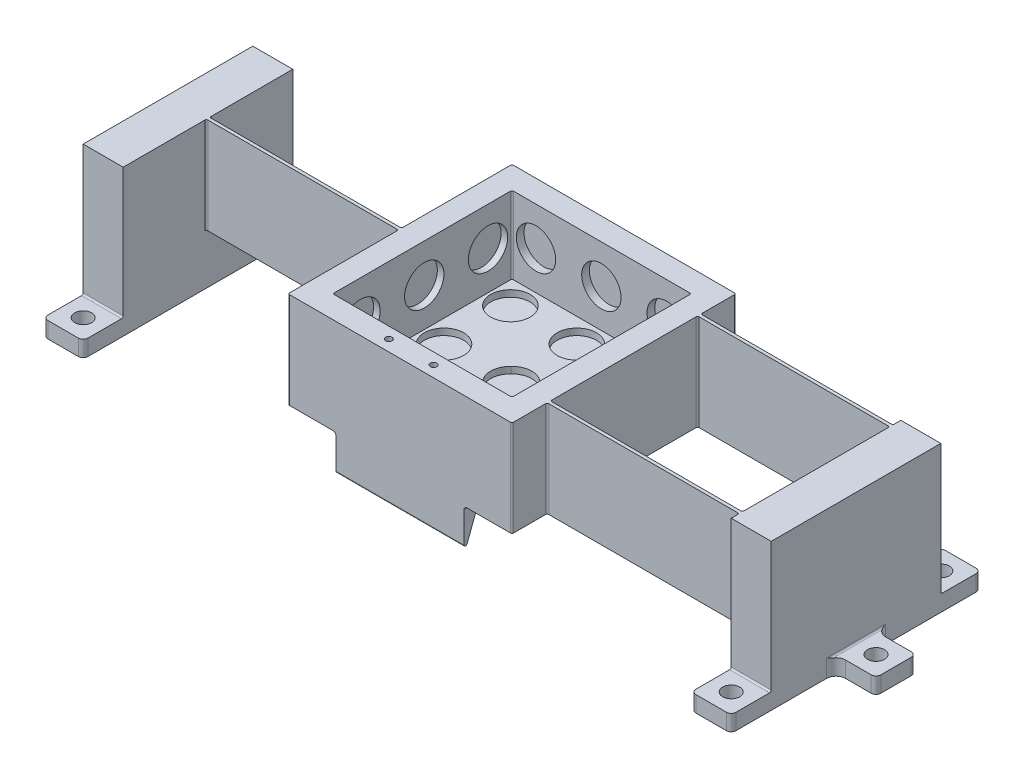
SolidWorks part; units mm, degrees
ref_plane "Front Plane" through (0, 0, 0) normal (0, 0, 1) x (1, 0, 0)
ref_plane "Top Plane" through (0, 0, 0) normal (0, 1, 0) x (1, 0, 0)
ref_plane "Right Plane" through (0, 0, 0) normal (1, 0, 0) x (0, 0, -1)
sketch "Sketch1" plane through (0, 0, 0) normal (0, 1, 0) x (1, 0, 0)
  line L1 (-35, -35) -> (35, -35)
  line L2 (-35, -35) -> (-35, 35)
  line L3 (-35, 35) -> (35, 35)
  line L4 (35, -35) -> (35, 35)
  line L5 (-35, -35) -> (35, 35) construction
  line L6 (-35, 35) -> (35, -35) construction
  point P0 (0, 0)
  dimension "D1" = 70
  dimension "D2" = 70
extrude "Boss-Extrude1" add sketch "Sketch1" along normal blind 30
shell "Shell1" thickness 7 removed face at (0, 30, 0)
sketch "Sketch2" plane through (0, 30, 0) normal (0, 1, 0) x (1, 0, 0)
  line L0 (-35, 35) -> (-35, -35) construction
  line L1 (-28, -28) -> (28, -28) construction
  line L2 (-28, -28) -> (-28, 28) construction
  line L3 (-28, 28) -> (28, 28) construction
  line L4 (28, -28) -> (28, 28) construction
  line L5 (-28, -28) -> (28, 28) construction
  line L6 (-28, 28) -> (28, -28) construction
  line L7 (35, 35) -> (-35, 35) construction
  point P0 (0, 0)
  dimension "D1" = 7
  dimension "D2" = 7
sketch "Sketch3" plane through (35, 0, 0) normal (1, 0, 0) x (0, 0, -1)
  line L0 (-35, 30) -> (35, 30) construction
  line L1 (-24, 30) -> (-23, 30)
  line L2 (-24, 30) -> (-24, 0)
  line L3 (-24, 0) -> (-23, 0)
  line L4 (-23, 30) -> (-23, 0)
  line L5 (-35, 0) -> (35, 0) construction
  line L6 (-28, 30) -> (28, 30) construction
  line L7 (-0.5, 30) -> (0.5, 30)
  line L8 (-0.5, 30) -> (-0.5, 0)
  line L9 (-0.5, 0) -> (0.5, 0)
  line L10 (0.5, 30) -> (0.5, 0)
  line L11 (28, 30) -> (-28, 30) construction
  line L12 (24, 30) -> (23, 30)
  line L13 (24, 30) -> (24, 0)
  line L14 (24, 0) -> (23, 0)
  line L15 (23, 30) -> (23, 0)
  line L16 (-23.5, 30) -> (-23.5, 0) construction
  line L17 (0, 30) -> (0, 0) construction
  line L18 (23.5, 0) -> (23.5, 30) construction
  dimension "D1" = 23
  dimension "D2" = 23
  dimension "D3" = 1
extrude "Boss-Extrude2" add sketch "Sketch3" along normal blind 60
sketch "Sketch5" plane through (95, 0, 0) normal (1, 0, 0) x (0, 0, -1)
  line L0 (-24, 30) -> (-24, 0) construction
  line L1 (-26.5, 30) -> (26.5, 30)
  line L2 (-26.5, 30) -> (-26.5, 0)
  line L3 (-26.5, 0) -> (26.5, 0)
  line L4 (26.5, 30) -> (26.5, 0)
  line L5 (28, 30) -> (-28, 30) construction
  line L6 (24, 0) -> (35, 0) construction
  line L7 (24, 0) -> (24, 30) construction
  dimension "D1" = 2.5
  dimension "D2" = 2.5
extrude "Boss-Extrude3" add sketch "Sketch5" along normal blind 12.5
sketch "Sketch6" plane through (0, 0, 0) normal (0, -1, 0) x (1, 0, 0)
  line L1 (95, 26.5) -> (107.5, 26.5)
  line L2 (95, 26.5) -> (95, -26.5)
  line L3 (95, -26.5) -> (107.5, -26.5)
  line L4 (107.5, 26.5) -> (107.5, -26.5)
extrude "Boss-Extrude4" add sketch "Sketch6" along normal blind 15.75
sketch "Sketch8" plane through (0, -15.75, 0) normal (0, -1, 0) x (1, 0, 0)
  line L1 (107.5, -26.5) -> (95, -26.5)
  line L2 (107.5, -26.5) -> (107.5, -39)
  line L3 (107.5, -39) -> (95, -39)
  line L4 (95, -26.5) -> (95, -39)
  line L5 (107.5, 26.5) -> (95, 26.5)
  line L6 (107.5, 26.5) -> (107.5, 39)
  line L7 (107.5, 39) -> (95, 39)
  line L8 (95, 26.5) -> (95, 39)
  line L13 (107.5, -26.5) -> (107.5, 26.5) construction
  line L14 (120, -6.25) -> (107.5, -6.25)
  line L15 (120, -6.25) -> (120, 6.25)
  line L16 (120, 6.25) -> (107.5, 6.25)
  line L17 (107.5, -6.25) -> (107.5, 6.25)
  line L18 (120, -6.25) -> (107.5, 6.25) construction
  line L19 (120, 6.25) -> (107.5, -6.25) construction
  line L20 (95, 0) -> (120, 0) construction
  line L21 (95, 0.5) -> (95, -0.5) construction
  point P13 (113.75, 0)
  point P19 (107.5, 0)
  point P20 (107.5, 0)
extrude "Boss-Extrude5" add sketch "Sketch8" against normal blind 5
hole_wizard "Ø5.0mm Dowel Hole1" positions "Sketch9" profile "Sketch10" hole size "Ø5.0" standard "ANSI Metric"
sketch "Sketch9" plane through (0, -10.75, 0) normal (0, 1, 0) x (1, 0, 0)
  line L0 (101.25, 39) -> (101.25, 32.75) construction
  line L1 (95, 39) -> (107.5, 39) construction
  line L2 (101.25, 32.75) -> (107.5, 32.75) construction
  line L3 (107.5, 39) -> (107.5, 26.5) construction
  line L5 (107.5, 0) -> (113.75, 0) construction
  line L6 (107.5, -6.25) -> (107.5, 6.25) construction
  line L7 (113.75, 0) -> (113.75, 6.25) construction
  line L8 (107.5, 6.25) -> (120, 6.25) construction
  line L10 (101.25, -26.5) -> (101.25, -32.75) construction
  line L11 (95, -26.5) -> (107.5, -26.5) construction
  line L12 (101.25, -32.75) -> (107.5, -32.75) construction
  line L13 (107.5, -26.5) -> (107.5, -39) construction
  point P0 (101.25, 32.75)
  point P2 (113.75, 0)
  point P4 (101.25, -32.75)
sketch "Sketch10" plane through (101.25, -10.75, -32.75) normal (1, 0, 0) x (0, 0, 1)
  line L0 (0, 0) -> (0, 18.1023)
  line L1 (0, 18.1023) -> (2.65, 16.51)
  line L2 (2.65, 16.51) -> (2.65, 0)
  line L5 (2.65, 0) -> (0, 0)
  line L10 (0, 18.1023) -> (-2.65, 16.51) construction
  line L11 (0, -6.35) -> (0, 107.95) construction
  dimension "Hole Dia." = 5.3
  dimension "Hole Depth" = 16.51
  dimension "Drill Angle" = 118
mirror "Mirror1" about plane through (0, 0, 0) normal (1, 0, 0) of "Boss-Extrude2", "Boss-Extrude3", "Boss-Extrude5", "Boss-Extrude4", "Ø5.0mm Dowel Hole1"
sketch "Sketch25" plane through (0, 30, 0) normal (0, 1, 0) x (1, 0, 0)
  line L1 (-95, 24) -> (-35, 24)
  line L2 (-95, 24) -> (-95, 23)
  line L3 (-95, 23) -> (-35, 23)
  line L4 (-35, 24) -> (-35, 23)
  line L5 (-95, -23) -> (-35, -23)
  line L6 (-95, -23) -> (-95, -24)
  line L7 (-95, -24) -> (-35, -24)
  line L8 (-35, -23) -> (-35, -24)
extrude "Cut-Extrude7" cut sketch "Sketch25" against normal through all both and the other way through all
fillet "Fillet2" radius 1.5 12 edges at (120, -13.25, 6.25) (120, -13.25, -6.25) (107.5, -13.25, -39) (95, -13.25, -39) (107.5, -13.25, 39) (95, -13.25, 39) (-95, -13.25, -39) (-107.5, -13.25, -39) (-120, -13.25, -6.25) (-120, -13.25, 6.25) (-95, -13.25, 39) (-107.5, -13.25, 39)
sketch "Sketch11" plane through (0, 6, 0) normal (0, 1, 0) x (1, 0, 0)
  line L26 (-28, -28) -> (-28, 28) construction
  line L32 (-28, -28) -> (28, -28) construction
  circle A0 centre (-21, -21) radius 6.15
  dimension "D1" = 12.3
  dimension "D2" = 0.85
  dimension "D3" = 0.85
extrude "Cut-Extrude1" cut sketch "Sketch11" against normal blind 2.05
pattern_linear "LPattern1" count 3 spacing 20.75 along (1, 0, 0) count 3 spacing 20.75 along (0, 0, -1) of "Cut-Extrude1"
sketch "Sketch14" plane through (0, 6, 0) normal (0, 1, 0) x (1, 0, 0)
  line L0 (-28, 0) -> (0, 0) construction
  line L1 (-28, 28) -> (-28, -28) construction
  line L2 (0, 0) -> (0, -28) construction
  line L3 (-28, -28) -> (28, -28) construction
  circle A0 centre (0, 0) radius 6.15
  dimension "D1" = 12.3
extrude "Cut-Extrude4" cut sketch "Sketch14" against normal blind 2.05
sketch "Sketch12" plane through (-28, 0, 0) normal (1, 0, 0) x (0, 0, -1)
  line L5 (-28, 18) -> (-19.35, 18) construction
  line L6 (-28, 30) -> (-28, 6) construction
  circle A0 centre (-19.35, 18) radius 6.15
  dimension "D1" = 12.3
  dimension "D2" = 2.5
extrude "Cut-Extrude2" cut sketch "Sketch12" against normal blind 2.05
pattern_linear "LPattern2" count 3 spacing 19.925 along (0, 0, -1) of "Cut-Extrude2"
sketch "Sketch13" plane through (0, 0, -28) normal (0, 0, -1) x (-1, 0, 0)
  line L6 (-28, 30) -> (-28, 6) construction
  line L7 (-20.35, 18) -> (-28, 18) construction
  circle A0 centre (-20.35, 18) radius 6.15
  dimension "D1" = 12.3
  dimension "D3" = 1.5
extrude "Cut-Extrude3" cut sketch "Sketch13" along normal blind 2.4
pattern_linear "LPattern3" count 3 spacing 20.425 along (-1, 0, 0) of "Cut-Extrude3"
mirror "Mirror2" about plane through (0, 0, 0) normal (1, 0, 0) of "LPattern2", "Cut-Extrude2"
sketch "Sketch24" plane through (0, 30, 0) normal (0, 1, 0) x (1, 0, 0)
  line L1 (35, 0.5) -> (95, 0.5)
  line L2 (35, 0.5) -> (35, -0.5)
  line L3 (35, -0.5) -> (95, -0.5)
  line L4 (95, 0.5) -> (95, -0.5)
extrude "Cut-Extrude6" cut sketch "Sketch24" against normal through all both and the other way through all
fillet "Fillet4" radius 0.5 4 edges at (-35, 15, 35) (35, 15, 35) (-35, 15, -35) (35, 15, -35)
sketch "Sketch19" plane through (0, 0, 0) normal (1, 0, 0) x (0, 0, -1)
  line L0 (-30, 0) -> (-35, -13.25)
  line L1 (-35, -13.25) -> (-35, 0)
  line L2 (-35, 0) -> (-30, 0)
  line L3 (0, 0) -> (-30, 0) construction
  line L4 (37.5, -15.75) -> (-37.5, -15.75) construction
  dimension "D1" = 5
  dimension "D2" = 30
  dimension "D3" = 2.5
extrude "Boss-Extrude8" add sketch "Sketch19" along normal mid plane 40
sketch "Sketch20" plane through (0, 0, 0) normal (1, 0, 0) x (0, 0, -1)
  line L0 (-35, 20) -> (-42.5, 20)
  line L1 (-42.5, 20) -> (-42.5, 30)
  line L2 (-26.5, 30) -> (-42.5, 30) construction
  line L5 (-42.5, 30) -> (-40, 30)
  line L6 (-40, 30) -> (-40, 22.5)
  line L7 (-40, 22.5) -> (-35, 22.5)
  line L8 (-35, 22.5) -> (-35, 20)
  line L9 (-35, 30) -> (-35, 0) construction
  line L10 (-35, 0) -> (-35, 30) construction
  dimension "D1" = 5
  dimension "D2" = 10
  dimension "D3" = 2.5
  dimension "D4" = 2.5
extrude "Place For Sensor" [suppressed] add sketch "Sketch20" along normal mid plane 10
fillet "Place For Sensor Fillet5" [suppressed] radius 0.5
fillet "Place For Sensor Fillet6" [suppressed] radius 1.5
hole_wizard "Place For Sensor Ø3.0mm Dowel Hole2" [suppressed] positions "Sketch21" profile "Sketch22" hole size "Ø3.0" standard "ANSI Metric"
sketch "Sketch21" [suppressed] plane through (0, 0, 32.5) normal (0, 0, 1) x (1, 0, 0)
  line L0 (-2.5, 27.5) -> (2.5, 27.5) construction
  line L2 (-18, 30) -> (18, 30) construction
  line L3 (-5, 28.5) -> (-5, 20.5) construction
  line L4 (5, 28.5) -> (5, 20.5) construction
  point P0 (-2.5, 27.5)
  point P2 (2.5, 27.5)
  dimension "D1" = 2.5
  dimension "D2" = 2.5
  dimension "D3" = 2.5
sketch "Sketch22" plane through (-2.5, 27.5, 32.5) normal (1, 0, 0) x (0, -1, 0)
  line L0 (0, 0) -> (0, 2.5)
  line L1 (0, 2.5) -> (1.65, 2.5)
  line L2 (1.65, 2.5) -> (1.65, 0)
  line L5 (1.65, 0) -> (0, 0)
  line L11 (0, -6.35) -> (0, 107.95) construction
  dimension "Thru Hole Dia." = 3.3
  dimension "Thru Hole Depth" = 2.5
sketch "Sketch23" plane through (0, 30, 0) normal (0, 1, 0) x (1, 0, 0)
  line L1 (-28, -28) -> (28, -28) construction
  circle A0 centre (-7, -31.5) radius 1
  circle A1 centre (7, -31.5) radius 1
  dimension "D4" = 2
  dimension "D1" = 3.5
  dimension "D2" = 14
  dimension "D3" = 7
extrude "Cut-Extrude5" cut sketch "Sketch23" against normal blind 6
fillet "Fillet3" radius 0.5 4 edges at (28, 18, -28) (-28, 18, -28) (28, 18, 28) (-28, 18, 28)
fillet "Fillet1" radius 0.5 16 edges at (101.25, -10.75, -26.5) (101.25, -10.75, 26.5) (-95, 15, 0.5) (-95, 15, -0.5) (-35, 15, 0.5) (-35, 15, -0.5) (-101.25, -10.75, -26.5) (-101.25, -10.75, 26.5) (35, 15, 24) (35, 15, 23) (95, 15, 24) (95, 15, 23) (35, 15, -24) (35, 15, -23) (95, 15, -24) (95, 15, -23)
fillet "Fillet5" radius 0.5 1 edges at (0, -13.25, 35)
fillet "Fillet6" radius 1 3 edges at (-20, 0, 32.5) (20, 0, 32.5) (0, 0, 30)
fillet "Fillet8" radius 3 4 edges at (107.5, -13, 6.25) (107.5, -13, -6.25) (-107.5, -13, -6.25) (-107.5, -13, 6.25)
